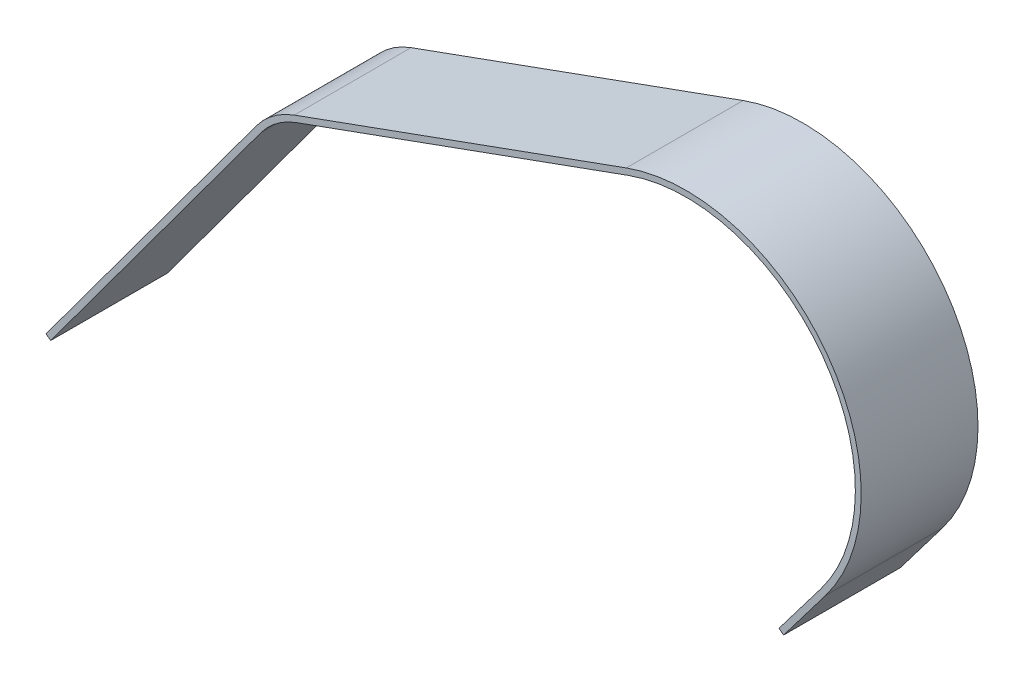
SolidWorks part; units mm, degrees
material "AISI 1020"
ref_plane "Front Plane" through (0, 0, 0) normal (0, 0, 1) x (1, 0, 0)
ref_plane "Top Plane" through (0, 0, 0) normal (0, 1, 0) x (1, 0, 0)
ref_plane "Right Plane" through (0, 0, 0) normal (1, 0, 0) x (0, 0, -1)
sketch "Sketch1" plane through (0, 0, 0) normal (0, 0, 1) x (1, 0, 0)
  line L0 (-36.5682, 0.9207) -> (143.9526, 66.3011)
  line L1 (-21.4316, -40.8727) -> (13.1807, -28.3369) construction
  line L6 (-36.5682, 0.9207) -> (-21.4316, -40.8727) construction
  line L14 (229.4691, -110.8747) -> (252.2647, -80.8348)
  line L15 (239.0655, -98.2286) -> (240.3301, -99.1882) construction
  line L19 (-57.2078, -14.4934) -> (-171.5307, -169.5402)
  line L23 (-163.3872, -155.8209) -> (-162.1095, -156.763) construction
  line L28 (143.9526, 66.3011) -> (194.1881, -72.4034) construction
  arc A0 (-57.2078, -14.4934) -> (-36.5682, 0.9207) centre (-21.4316, -40.8727) cw
  arc A10 (-190.1171, -186.0404) -> (-190.1067, -160.6404) centre (-190.1119, -173.3404) ccw construction
  arc A11 (143.9526, 66.3011) -> (252.2647, -80.8348) centre (176.3881, -23.2561) cw
  circle A12 centre (-21.4316, -40.8727) radius 6 construction
  circle A13 centre (231.071, -129.7727) radius 12.7 construction
  dimension "D5" = 44.45
  dimension "D3" = 15.875
  dimension "D2" = 95.25
  dimension "D1" = 15.875
extrude "Extrude-Thin1" add sketch "Sketch1" along normal blind 63.5 thin thin type one direction reverse wall 3.175
